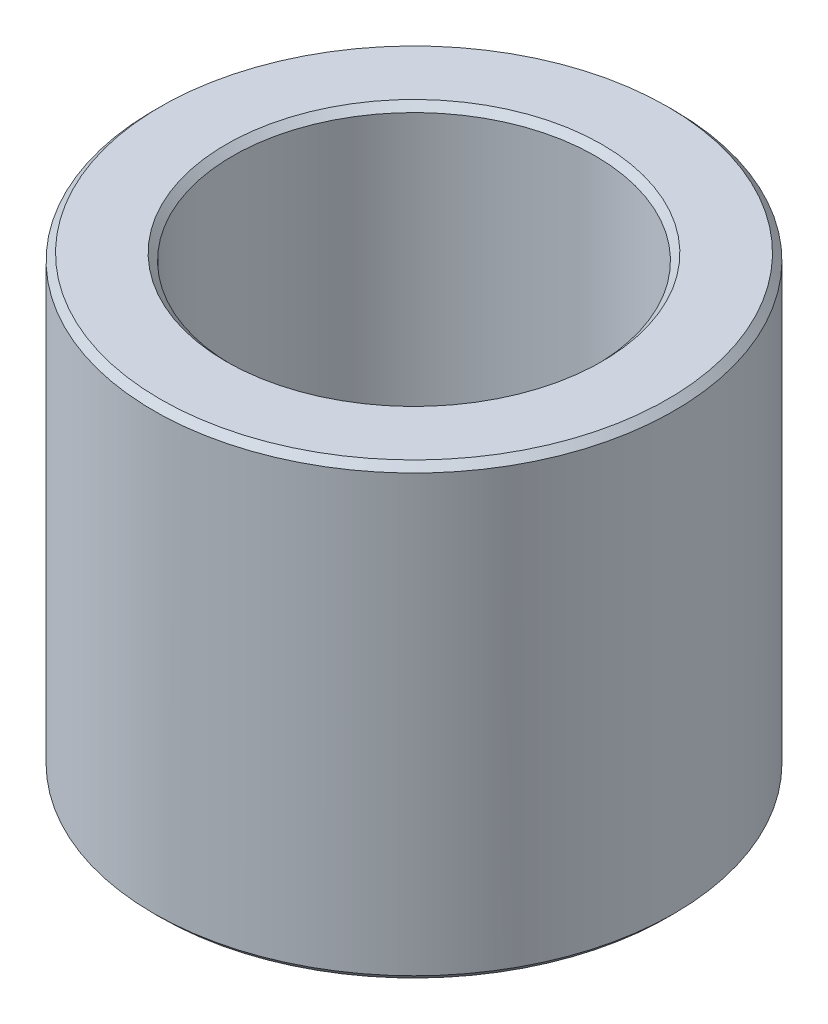
SolidWorks part; units mm, degrees
ref_plane "Front Plane" through (0, 0, 0) normal (0, 0, 1) x (1, 0, 0)
ref_plane "Top Plane" through (0, 0, 0) normal (0, 1, 0) x (1, 0, 0)
ref_plane "Right Plane" through (0, 0, 0) normal (1, 0, 0) x (0, 0, -1)
sketch "Sketch1" plane through (0, 0, 0) normal (0, 1, 0) x (1, 0, 0)
  circle A0 centre (0, 0) radius 35
  dimension "SLEEVE_OD" = 70
extrude "Boss-Extrude1" add sketch "Sketch1" along normal blind 60.3581
sketch "Sketch2" plane through (0, 0, 0) normal (0, 1, 0) x (1, 0, 0)
  circle A0 centre (0, 0) radius 24.399
  dimension "BORE_D" = 48.798
extrude "Cut-Extrude1" cut sketch "Sketch2" along normal through all
chamfer "Chamfer1" distance 0.894 angle 45 4 edges at (0, 60.3581, 24.399) (0, 0, 24.399) (0, 0, 35) (0, 60.3581, 35)
